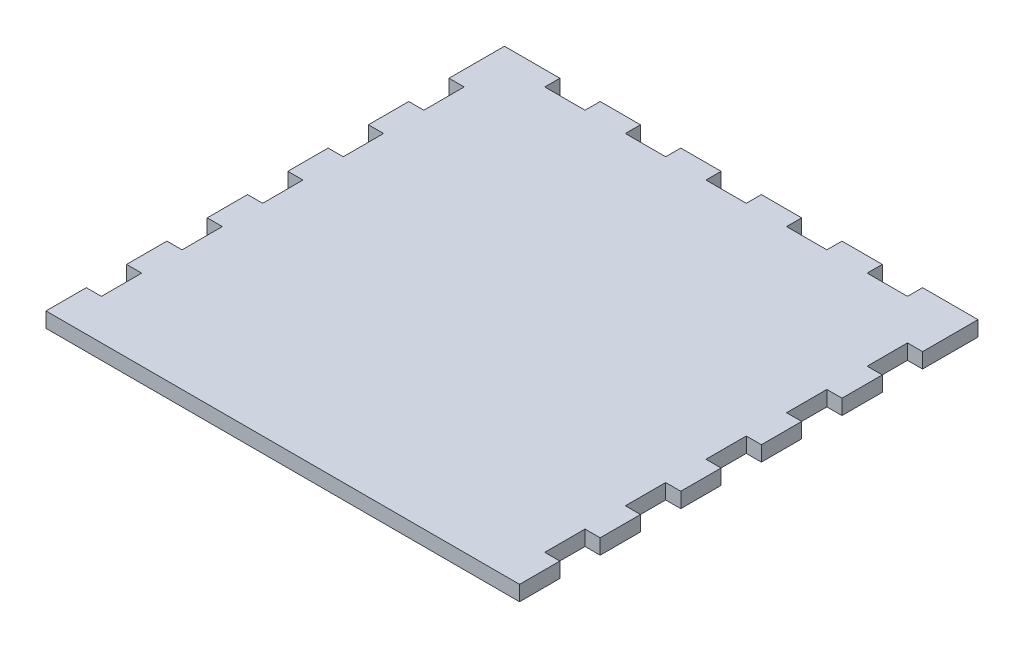
SolidWorks part; units mm, degrees
ref_plane "Front Plane" through (0, 0, 0) normal (0, 0, 1) x (1, 0, 0)
ref_plane "Top Plane" through (0, 0, 0) normal (0, 1, 0) x (1, 0, 0)
ref_plane "Right Plane" through (0, 0, 0) normal (1, 0, 0) x (0, 0, -1)
sketch "Sketch1" plane through (0, 0, 0) normal (0, 1, 0) x (1, 0, 0)
  line L1 (-139.7, -139.7) -> (139.7, -139.7)
  line L2 (-139.7, -139.7) -> (-139.7, 139.7)
  line L3 (-139.7, 139.7) -> (139.7, 139.7)
  line L4 (139.7, -139.7) -> (139.7, 139.7)
  line L5 (-139.7, -139.7) -> (139.7, 139.7) construction
  line L6 (-139.7, 139.7) -> (139.7, -139.7) construction
  point P0 (0, 0)
  dimension "D1" = 279.4
  dimension "D2" = 279.4
extrude "Boss-Extrude1" add sketch "Sketch1" along normal blind 9.525
sketch "Sketch2" plane through (139.7, 0, 0) normal (1, 0, 0) x (0, 0, -1)
  line L0 (-139.7, 9.525) -> (139.7, 9.525) construction
  line L1 (-139.7, 0) -> (-114.3, 0)
  line L2 (-139.7, 0) -> (-139.7, 9.525)
  line L3 (-139.7, 9.525) -> (-114.3, 9.525)
  line L4 (-114.3, 0) -> (-114.3, 9.525)
  dimension "D1" = 25.4
extrude "Boss-Extrude2" add sketch "Sketch2" along normal blind 9.525
pattern_linear "LPattern1" count 6 spacing 50.8 along (0, 0, -1) of "Boss-Extrude2"
mirror "Mirror1" about plane through (0, 0, 0) normal (1, 0, 0) of "LPattern1"
sketch "Sketch3" plane through (0, 0, -139.7) normal (0, 0, -1) x (-1, 0, 0)
  line L0 (-149.225, 9.525) -> (149.225, 9.525) construction
  line L1 (-139.7, 9.525) -> (-114.3, 9.525)
  line L2 (-139.7, 9.525) -> (-139.7, 0)
  line L3 (-139.7, 0) -> (-114.3, 0)
  line L4 (-114.3, 9.525) -> (-114.3, 0)
  line L5 (-149.225, 0) -> (149.225, 0) construction
  line L6 (-149.225, 0) -> (-149.225, 9.525) construction
  dimension "D1" = 9.525
  dimension "D2" = 25.4
extrude "Boss-Extrude3" add sketch "Sketch3" along normal blind 9.525
pattern_linear "LPattern2" count 6 spacing 50.8 along (-1, 0, 0) of "Boss-Extrude3"
sketch "Sketch5" plane through (0, 0, -139.7) normal (0, 0, -1) x (-1, 0, 0)
  line L0 (158.9088, 0) -> (-158.9088, 0) construction
  line L1 (-149.225, 9.525) -> (-139.7, 9.525)
  line L2 (-149.225, 9.525) -> (-149.225, 0)
  line L3 (-149.225, 0) -> (-139.7, 0)
  line L4 (-139.7, 9.525) -> (-139.7, 0)
  line L5 (-139.7, 9.525) -> (-139.7, 0) construction
extrude "Boss-Extrude4" add sketch "Sketch5" along normal blind 9.525
mirror "Mirror2" about plane through (0, 0, 0) normal (1, 0, 0) of "Boss-Extrude4"
